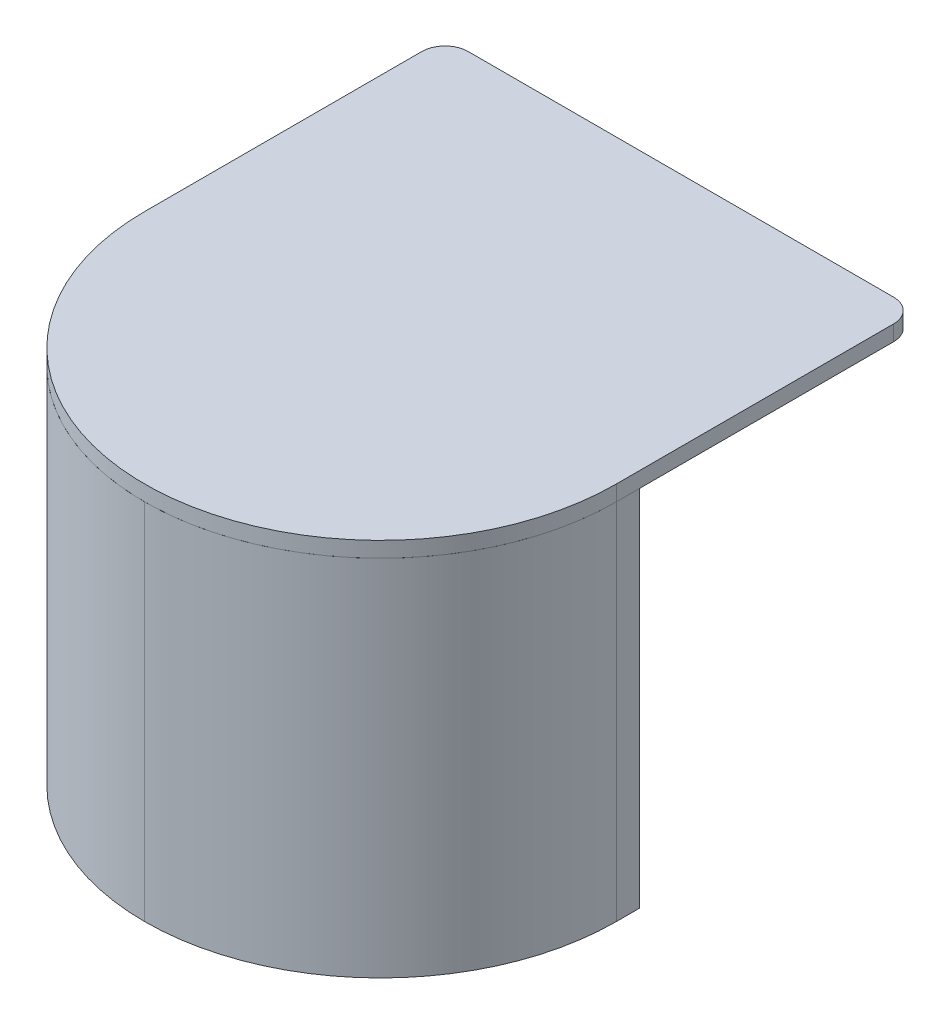
SolidWorks part; units mm, degrees
ref_plane "정면" through (0, 0, 0) normal (0, 0, 1) x (1, 0, 0)
ref_plane "윗면" through (0, 0, 0) normal (0, 1, 0) x (1, 0, 0)
ref_plane "우측면" through (0, 0, 0) normal (1, 0, 0) x (0, 0, -1)
sketch "스케치1" plane through (0, 0, 0) normal (0, 1, 0) x (1, 0, 0)
  line L1 (-30.5, -16.75) -> (30.5, -16.75)
  line L2 (-30.5, -16.75) -> (-30.5, 16.75)
  line L3 (-30.5, 16.75) -> (30.5, 16.75)
  line L4 (30.5, -16.75) -> (30.5, 16.75)
  line L5 (-30.5, -16.75) -> (30.5, 16.75) construction
  line L6 (-30.5, 16.75) -> (30.5, -16.75) construction
  point P0 (0, 0)
  dimension "D1" = 61
  dimension "D2" = 33.5
extrude "보스-돌출1" add sketch "스케치1" along normal blind 50
sketch "스케치2" plane through (0, 0, -16.75) normal (0, 0, -1) x (-1, 0, 0)
  line L0 (0, 0) -> (0, 50) construction
  line L1 (-30.5, 50) -> (30.5, 50) construction
  line L2 (-30.5, 25) -> (30.5, 25) construction
  line L3 (-30.5, 50) -> (-30.5, 0) construction
  line L4 (30.5, 50) -> (30.5, 0) construction
  line L5 (-30.5, 0) -> (30.5, 0) construction
  line L6 (-27.5, 3) -> (27.5, 3)
  line L7 (-27.5, 3) -> (-27.5, 47)
  line L8 (-27.5, 47) -> (27.5, 47)
  line L9 (27.5, 3) -> (27.5, 47)
  line L10 (-27.5, 3) -> (27.5, 47) construction
  line L11 (-27.5, 47) -> (27.5, 3) construction
  point P11 (0, 25)
  dimension "D1" = 3
  dimension "D2" = 3
extrude "컷-돌출1" cut sketch "스케치2" against normal blind 30.5
fillet "필렛3" radius 27.5 2 edges at (-27.5, 25, 13.75) (27.5, 25, 13.75)
fillet "필렛4" radius 30.5 2 edges at (-30.5, 25, 16.75) (30.5, 25, 16.75)
sketch "스케치3" plane through (0, 0, 0) normal (0, -1, 0) x (1, 0, 0)
  line L1 (-30.5, -13.75) -> (30.5, -13.75) construction
  circle A0 centre (0, -13.75) radius 23.5
  arc A1 (30.5, -13.75) -> (0, 16.75) centre (0, -13.75) ccw construction
  dimension "D1" = 7
extrude "컷-돌출2" cut sketch "스케치3" against normal blind 30.5
sketch "스케치5" plane through (0, 47, 0) normal (0, -1, 0) x (1, 0, 0)
  line L0 (-23.5, -13.75) -> (23.5, -13.75) construction
  arc A0 (23.3077, -16.75) -> (-23.3077, -16.75) centre (0, -13.75) ccw construction
  circle A1 centre (0, -13.75) radius 16
extrude "컷-돌출4" cut sketch "스케치5" against normal blind 30.5
fillet "필렛5" radius 4 2 edges at (15.7162, 48.5, -16.75) (-15.7162, 48.5, -16.75)
fillet "필렛6" radius 2 2 edges at (23.3077, 1.5, -16.75) (-23.3077, 1.5, -16.75)
sketch "스케치6" plane through (0, 0, -16.75) normal (0, 0, -1) x (-1, 0, 0)
  line L0 (30.5, 50) -> (30.5, 0) construction
  line L1 (-30.5, 50) -> (30.5, 50)
  line L2 (-30.5, 50) -> (-30.5, 47)
  line L3 (-30.5, 47) -> (30.5, 47)
  line L4 (30.5, 50) -> (30.5, 47)
  dimension "D1" = 3
extrude "컷-돌출5" cut sketch "스케치6" against normal blind 400
sketch "스케치8" plane through (0, 47, 0) normal (0, 1, 0) x (1, 0, 0)
  line L0 (30.5, 13.75) -> (30.5, 16.75) construction
  line L1 (-30.5, 16.75) -> (30.5, 16.75)
  line L2 (-30.5, 16.75) -> (-30.5, 52.5966)
  line L3 (-30.5, 52.5966) -> (30.5, 52.5966)
  line L4 (30.5, 16.75) -> (30.5, 52.5966)
  line L5 (-30.5, 13.75) -> (30.5, 13.75)
  line L6 (-30.5, 16.75) -> (30.5, 16.75)
  line L7 (-30.5, 16.75) -> (-30.5, 13.75)
  line L8 (-30.5, 13.75) -> (30.5, 13.75)
  line L9 (30.5, 16.75) -> (30.5, 13.75)
  arc A0 (-30.5, 13.75) -> (30.5, 13.75) centre (0, 13.75) ccw
  point P7 (30.5, 15.25)
  line M5 (-27.5, 16.75) -> (-30.5, 16.75)
  line M6 (-30.5, 16.75) -> (-30.5, 13.75)
  arc M7 (-30.5, 13.75) -> (0, -16.75) centre (0, 13.75) ccw
  arc M8 (0, -16.75) -> (30.5, 13.75) centre (0, 13.75) ccw
  line M9 (30.5, 13.75) -> (30.5, 16.75)
  line M10 (30.5, 16.75) -> (27.5, 16.75)
  line M11 (27.5, 16.75) -> (27.5, 13.75)
  arc M12 (27.5, 13.75) -> (0, -13.75) centre (0, 13.75) cw
  arc M13 (0, -13.75) -> (-27.5, 13.75) centre (0, 13.75) cw
  line M14 (-27.5, 13.75) -> (-27.5, 16.75)
  dimension "D1" = 0
extrude "보스-돌출2" add sketch "스케치8" along normal blind 2 separate body contours L5 M13 M12 | L5 L1 M14 M11 | L4 L3 L2 L1 M10 M5 | L5 M7 M8 M12 M13 | L5 M11 M9 M10 | L5 M6 M14 M5 region at (0, 47, -34.6733) region at (-29, 47, -15.25) region at (0, 47, -15.25) region at (-29, 47, -13.068) region at (29, 47, -15.25) region at (0, 47, -2.0786)
fillet "필렛7" radius 3 2 edges at (-30.5, 48, -52.5966) (30.5, 48, -52.5966)
